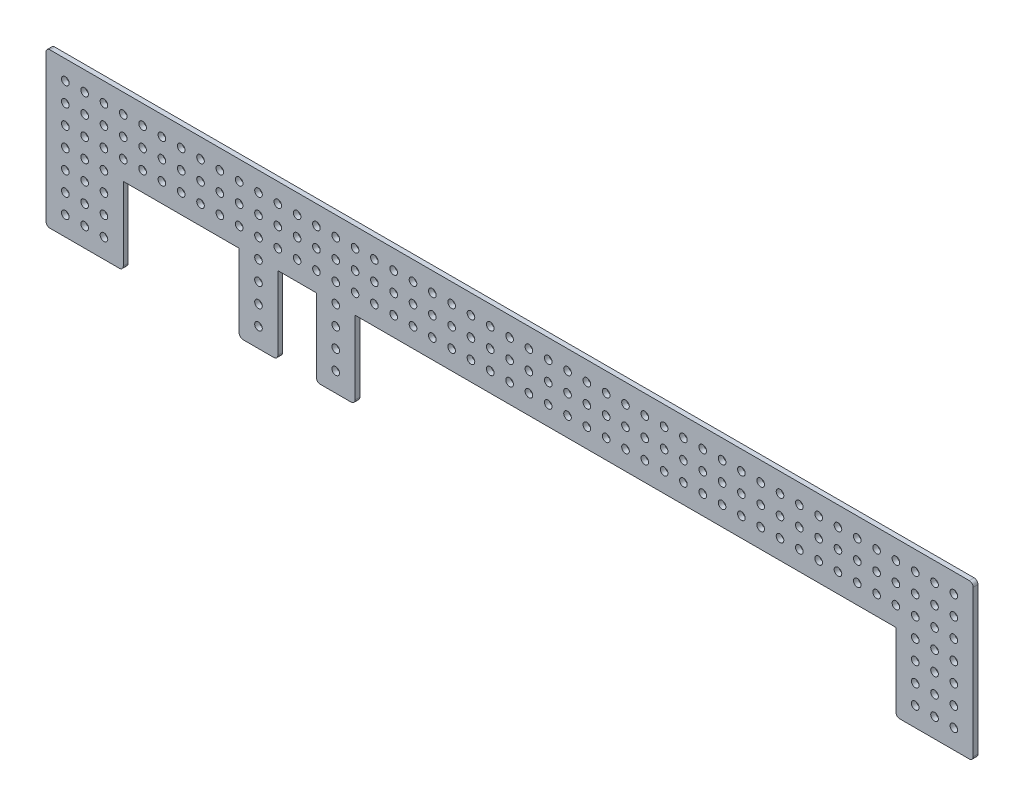
SolidWorks part; units mm, degrees
ref_plane "Front Plane" through (0, 0, 0) normal (0, 0, 1) x (1, 0, 0)
ref_plane "Top Plane" through (0, 0, 0) normal (0, 1, 0) x (1, 0, 0)
ref_plane "Right Plane" through (0, 0, 0) normal (1, 0, 0) x (0, 0, -1)
sketch "Sketch2" plane through (0, 0, 0) normal (0, 0, 1) x (1, 0, 0)
  line L1 (-478.1332, -46.4778) -> (126.3868, -46.4778)
  line L2 (-480.6732, -49.0178) -> (-480.6732, -97.2778)
  line L3 (-480.6732, -97.2778) -> (128.9268, -97.2778)
  line L4 (128.9268, -49.0178) -> (128.9268, -97.2778)
  line L5 (-480.6732, -97.2778) -> (-429.8732, -97.2778)
  line L6 (-480.6732, -97.2778) -> (-480.6732, -145.5378)
  line L7 (-478.1332, -148.0778) -> (-432.4132, -148.0778)
  line L8 (-429.8732, -97.2778) -> (-429.8732, -145.5378)
  line L9 (78.1268, -97.2778) -> (128.9268, -97.2778)
  line L10 (78.1268, -97.2778) -> (78.1268, -145.5378)
  line L11 (80.6668, -148.0778) -> (126.3868, -148.0778)
  line L12 (128.9268, -97.2778) -> (128.9268, -145.5378)
  arc A0 (78.1268, -145.5378) -> (80.6668, -148.0778) centre (80.6668, -145.5378) ccw
  arc A1 (126.3868, -148.0778) -> (128.9268, -145.5378) centre (126.3868, -145.5378) ccw
  arc A2 (126.3868, -46.4778) -> (128.9268, -49.0178) centre (126.3868, -49.0178) cw
  arc A3 (-432.4132, -148.0778) -> (-429.8732, -145.5378) centre (-432.4132, -145.5378) ccw
  arc A4 (-480.6732, -145.5378) -> (-478.1332, -148.0778) centre (-478.1332, -145.5378) ccw
  arc A5 (-478.1332, -46.4778) -> (-480.6732, -49.0178) centre (-478.1332, -49.0178) ccw
  point P16 (78.1268, -148.0778)
  point P19 (128.9268, -148.0778)
  point P22 (128.9268, -46.4778)
  point P25 (-429.8732, -148.0778)
  point P28 (-480.6732, -148.0778)
  dimension "D7" = 2.54
  dimension "D1" = 50.8
  dimension "D2" = 609.6
  dimension "D3" = 50.8
  dimension "D4" = 50.8
  dimension "3" = 50.8
  dimension "D6" = 50.8
extrude "Boss-Extrude1" add sketch "Sketch2" along normal blind 3.175 contours L4 L1 L2 L3 | L8 L3 L6 L7 | L12 L3 L10 L11 region at (-175.8732, -71.88, 0) region at (-455.2732, -122.6511, 0) region at (103.5268, -122.6511, 0)
sketch "Sketch3" plane through (0, 0, 3.175) normal (0, 0, 1) x (1, 0, 0)
  line L0 (-478.1332, -46.4778) -> (126.3868, -46.4778) construction
  line L1 (-480.6732, -49.0178) -> (-480.6732, -145.5378) construction
  line L2 (-478.1332, -148.0778) -> (-432.4132, -148.0778) construction
  line L3 (80.6668, -148.0778) -> (126.3868, -148.0778) construction
  line L4 (78.1268, -97.2778) -> (78.1268, -145.5378) construction
  circle A0 centre (-467.9732, -59.1778) radius 2.505
  circle A1 centre (-455.2732, -59.1778) radius 2.505
  circle A2 centre (-442.5732, -59.1778) radius 2.505
  circle A3 centre (-429.8732, -59.1778) radius 2.505
  circle A4 centre (-417.1732, -59.1778) radius 2.505
  circle A5 centre (-404.4732, -59.1778) radius 2.505
  circle A6 centre (-391.7732, -59.1778) radius 2.505
  circle A7 centre (-379.0732, -59.1778) radius 2.505
  circle A8 centre (-366.3732, -59.1778) radius 2.505
  circle A9 centre (-353.6732, -59.1778) radius 2.505
  circle A10 centre (-340.9732, -59.1778) radius 2.505
  circle A11 centre (-328.2732, -59.1778) radius 2.505
  circle A12 centre (-315.5732, -59.1778) radius 2.505
  circle A13 centre (-302.8732, -59.1778) radius 2.505
  circle A14 centre (-290.1732, -59.1778) radius 2.505
  circle A15 centre (-277.4732, -59.1778) radius 2.505
  circle A16 centre (-264.7732, -59.1778) radius 2.505
  circle A17 centre (-252.0732, -59.1778) radius 2.505
  circle A18 centre (-239.3732, -59.1778) radius 2.505
  circle A19 centre (-226.6732, -59.1778) radius 2.505
  circle A20 centre (-213.9732, -59.1778) radius 2.505
  circle A21 centre (-201.2732, -59.1778) radius 2.505
  circle A22 centre (-188.5732, -59.1778) radius 2.505
  circle A23 centre (-175.8732, -59.1778) radius 2.505
  circle A24 centre (-163.1732, -59.1778) radius 2.505
  circle A25 centre (-150.4732, -59.1778) radius 2.505
  circle A26 centre (-137.7732, -59.1778) radius 2.505
  circle A27 centre (-125.0732, -59.1778) radius 2.505
  circle A28 centre (-112.3732, -59.1778) radius 2.505
  circle A29 centre (-99.6732, -59.1778) radius 2.505
  circle A30 centre (-86.9732, -59.1778) radius 2.505
  circle A31 centre (-74.2732, -59.1778) radius 2.505
  circle A32 centre (-61.5732, -59.1778) radius 2.505
  circle A33 centre (-48.8732, -59.1778) radius 2.505
  circle A34 centre (-36.1732, -59.1778) radius 2.505
  circle A35 centre (-23.4732, -59.1778) radius 2.505
  circle A36 centre (-10.7732, -59.1778) radius 2.505
  circle A37 centre (1.9268, -59.1778) radius 2.505
  circle A38 centre (14.6268, -59.1778) radius 2.505
  circle A39 centre (27.3268, -59.1778) radius 2.505
  circle A40 centre (40.0268, -59.1778) radius 2.505
  circle A41 centre (52.7268, -59.1778) radius 2.505
  circle A42 centre (65.4268, -59.1778) radius 2.505
  circle A43 centre (78.1268, -59.1778) radius 2.505
  circle A44 centre (90.8268, -59.1778) radius 2.505
  circle A45 centre (103.5268, -59.1778) radius 2.505
  circle A46 centre (116.2268, -59.1778) radius 2.505
  circle A47 centre (-455.2732, -71.8778) radius 2.505
  circle A48 centre (-442.5732, -71.8778) radius 2.505
  circle A49 centre (-429.8732, -71.8778) radius 2.505
  circle A50 centre (-417.1732, -71.8778) radius 2.505
  circle A51 centre (-404.4732, -71.8778) radius 2.505
  circle A52 centre (-391.7732, -71.8778) radius 2.505
  circle A53 centre (-379.0732, -71.8778) radius 2.505
  circle A54 centre (-366.3732, -71.8778) radius 2.505
  circle A55 centre (-353.6732, -71.8778) radius 2.505
  circle A56 centre (-340.9732, -71.8778) radius 2.505
  circle A57 centre (-328.2732, -71.8778) radius 2.505
  circle A58 centre (-315.5732, -71.8778) radius 2.505
  circle A59 centre (-302.8732, -71.8778) radius 2.505
  circle A60 centre (-290.1732, -71.8778) radius 2.505
  circle A61 centre (-277.4732, -71.8778) radius 2.505
  circle A62 centre (-264.7732, -71.8778) radius 2.505
  circle A63 centre (-252.0732, -71.8778) radius 2.505
  circle A64 centre (-239.3732, -71.8778) radius 2.505
  circle A65 centre (-226.6732, -71.8778) radius 2.505
  circle A66 centre (-213.9732, -71.8778) radius 2.505
  circle A67 centre (-201.2732, -71.8778) radius 2.505
  circle A68 centre (-188.5732, -71.8778) radius 2.505
  circle A69 centre (-175.8732, -71.8778) radius 2.505
  circle A70 centre (-163.1732, -71.8778) radius 2.505
  circle A71 centre (-150.4732, -71.8778) radius 2.505
  circle A72 centre (-137.7732, -71.8778) radius 2.505
  circle A73 centre (-125.0732, -71.8778) radius 2.505
  circle A74 centre (-112.3732, -71.8778) radius 2.505
  circle A75 centre (-99.6732, -71.8778) radius 2.505
  circle A76 centre (-86.9732, -71.8778) radius 2.505
  circle A77 centre (-74.2732, -71.8778) radius 2.505
  circle A78 centre (-61.5732, -71.8778) radius 2.505
  circle A79 centre (-48.8732, -71.8778) radius 2.505
  circle A80 centre (-36.1732, -71.8778) radius 2.505
  circle A81 centre (-23.4732, -71.8778) radius 2.505
  circle A82 centre (-10.7732, -71.8778) radius 2.505
  circle A83 centre (1.9268, -71.8778) radius 2.505
  circle A84 centre (14.6268, -71.8778) radius 2.505
  circle A85 centre (27.3268, -71.8778) radius 2.505
  circle A86 centre (40.0268, -71.8778) radius 2.505
  circle A87 centre (52.7268, -71.8778) radius 2.505
  circle A88 centre (65.4268, -71.8778) radius 2.505
  circle A89 centre (78.1268, -71.8778) radius 2.505
  circle A90 centre (90.8268, -71.8778) radius 2.505
  circle A91 centre (103.5268, -71.8778) radius 2.505
  circle A92 centre (116.2268, -71.8778) radius 2.505
  circle A93 centre (-455.2732, -84.5778) radius 2.505
  circle A94 centre (-442.5732, -84.5778) radius 2.505
  circle A95 centre (-429.8732, -84.5778) radius 2.505
  circle A96 centre (-417.1732, -84.5778) radius 2.505
  circle A97 centre (-404.4732, -84.5778) radius 2.505
  circle A98 centre (-391.7732, -84.5778) radius 2.505
  circle A99 centre (-379.0732, -84.5778) radius 2.505
  circle A100 centre (-366.3732, -84.5778) radius 2.505
  circle A101 centre (-353.6732, -84.5778) radius 2.505
  circle A102 centre (-340.9732, -84.5778) radius 2.505
  circle A103 centre (-328.2732, -84.5778) radius 2.505
  circle A104 centre (-315.5732, -84.5778) radius 2.505
  circle A105 centre (-302.8732, -84.5778) radius 2.505
  circle A106 centre (-290.1732, -84.5778) radius 2.505
  circle A107 centre (-277.4732, -84.5778) radius 2.505
  circle A108 centre (-264.7732, -84.5778) radius 2.505
  circle A109 centre (-252.0732, -84.5778) radius 2.505
  circle A110 centre (-239.3732, -84.5778) radius 2.505
  circle A111 centre (-226.6732, -84.5778) radius 2.505
  circle A112 centre (-213.9732, -84.5778) radius 2.505
  circle A113 centre (-201.2732, -84.5778) radius 2.505
  circle A114 centre (-188.5732, -84.5778) radius 2.505
  circle A115 centre (-175.8732, -84.5778) radius 2.505
  circle A116 centre (-163.1732, -84.5778) radius 2.505
  circle A117 centre (-150.4732, -84.5778) radius 2.505
  circle A118 centre (-137.7732, -84.5778) radius 2.505
  circle A119 centre (-125.0732, -84.5778) radius 2.505
  circle A120 centre (-112.3732, -84.5778) radius 2.505
  circle A121 centre (-99.6732, -84.5778) radius 2.505
  circle A122 centre (-86.9732, -84.5778) radius 2.505
  circle A123 centre (-74.2732, -84.5778) radius 2.505
  circle A124 centre (-61.5732, -84.5778) radius 2.505
  circle A125 centre (-48.8732, -84.5778) radius 2.505
  circle A126 centre (-36.1732, -84.5778) radius 2.505
  circle A127 centre (-23.4732, -84.5778) radius 2.505
  circle A128 centre (-10.7732, -84.5778) radius 2.505
  circle A129 centre (1.9268, -84.5778) radius 2.505
  circle A130 centre (14.6268, -84.5778) radius 2.505
  circle A131 centre (27.3268, -84.5778) radius 2.505
  circle A132 centre (40.0268, -84.5778) radius 2.505
  circle A133 centre (52.7268, -84.5778) radius 2.505
  circle A134 centre (65.4268, -84.5778) radius 2.505
  circle A135 centre (78.1268, -84.5778) radius 2.505
  circle A136 centre (90.8268, -84.5778) radius 2.505
  circle A137 centre (103.5268, -84.5778) radius 2.505
  circle A138 centre (116.2268, -84.5778) radius 2.505
  circle A139 centre (-467.9732, -71.8778) radius 2.505
  circle A140 centre (-467.9732, -84.5778) radius 2.505
  circle A141 centre (-467.9732, -135.3778) radius 2.505
  circle A142 centre (-455.2732, -135.3778) radius 2.505
  circle A143 centre (-442.5732, -135.3778) radius 2.505
  circle A144 centre (-455.2732, -122.6778) radius 2.505
  circle A145 centre (-442.5732, -122.6778) radius 2.505
  circle A146 centre (-455.2732, -109.9778) radius 2.505
  circle A147 centre (-442.5732, -109.9778) radius 2.505
  circle A148 centre (-455.2732, -97.2778) radius 2.505
  circle A149 centre (-442.5732, -97.2778) radius 2.505
  circle A150 centre (-455.2732, -84.5778) radius 2.505
  circle A151 centre (-442.5732, -84.5778) radius 2.505
  circle A152 centre (-455.2732, -71.8778) radius 2.505
  circle A153 centre (-442.5732, -71.8778) radius 2.505
  circle A154 centre (-467.9732, -122.6778) radius 2.505
  circle A155 centre (-467.9732, -109.9778) radius 2.505
  circle A156 centre (-467.9732, -97.2778) radius 2.505
  circle A157 centre (-467.9732, -84.5778) radius 2.505
  circle A158 centre (-467.9732, -71.8778) radius 2.505
  circle A159 centre (90.8268, -135.3778) radius 2.505
  circle A160 centre (103.5268, -135.3778) radius 2.505
  circle A161 centre (116.2268, -135.3778) radius 2.505
  circle A162 centre (103.5268, -122.6778) radius 2.505
  circle A163 centre (116.2268, -122.6778) radius 2.505
  circle A164 centre (103.5268, -109.9778) radius 2.505
  circle A165 centre (116.2268, -109.9778) radius 2.505
  circle A166 centre (103.5268, -97.2778) radius 2.505
  circle A167 centre (116.2268, -97.2778) radius 2.505
  circle A168 centre (103.5268, -84.5778) radius 2.505
  circle A169 centre (116.2268, -84.5778) radius 2.505
  circle A170 centre (103.5268, -71.8778) radius 2.505
  circle A171 centre (116.2268, -71.8778) radius 2.505
  circle A172 centre (90.8268, -122.6778) radius 2.505
  circle A173 centre (90.8268, -109.9778) radius 2.505
  circle A174 centre (90.8268, -97.2778) radius 2.505
  circle A175 centre (90.8268, -84.5778) radius 2.505
  circle A176 centre (90.8268, -71.8778) radius 2.505
  dimension "5.01mm" = 5.01
  dimension "D6" = 5.01
  dimension "D11" = 5.01
  dimension "D2" = 12.7
  dimension "D3" = 12.7
  dimension "D7" = 12.7
  dimension "D8" = 12.7
  dimension "D12" = 12.7
  dimension "D13" = 12.7
  dimension "D4" = 47
  dimension "D5" = 3
  dimension "D9" = 3
  dimension "D10" = 6
  dimension "D14" = 3
  dimension "D15" = 6
extrude "Cut-Extrude1" cut sketch "Sketch3" against normal through all
sketch "Sketch4" plane through (0, 0, 3.175) normal (0, 0, 1) x (1, 0, 0)
  line L0 (-429.8732, -97.2778) -> (78.1268, -97.2778) construction
  line L1 (-353.6732, -97.2778) -> (-328.2732, -97.2778)
  line L2 (-353.6732, -97.2778) -> (-353.6732, -145.5378)
  line L3 (-351.1332, -148.0778) -> (-330.8132, -148.0778)
  line L4 (-328.2732, -97.2778) -> (-328.2732, -145.5378)
  line L5 (-302.8732, -97.2778) -> (-277.4732, -97.2778)
  line L6 (-302.8732, -97.2778) -> (-302.8732, -145.5378)
  line L7 (-300.3332, -148.0778) -> (-280.0132, -148.0778)
  line L8 (-277.4732, -97.2778) -> (-277.4732, -145.5378)
  line L9 (-429.8732, -97.2778) -> (-429.8732, -145.5378) construction
  arc A0 (-280.0132, -148.0778) -> (-277.4732, -145.5378) centre (-280.0132, -145.5378) ccw
  arc A1 (-302.8732, -145.5378) -> (-300.3332, -148.0778) centre (-300.3332, -145.5378) ccw
  arc A2 (-330.8132, -148.0778) -> (-328.2732, -145.5378) centre (-330.8132, -145.5378) ccw
  arc A3 (-353.6732, -145.5378) -> (-351.1332, -148.0778) centre (-351.1332, -145.5378) ccw
  point P14 (-277.4732, -148.0778)
  point P17 (-302.8732, -148.0778)
  point P20 (-328.2732, -148.0778)
  point P23 (-353.6732, -148.0778)
  dimension "D7" = 2.54
  dimension "D1" = 25.4
  dimension "D2" = 50.8
  dimension "D3" = 76.2
  dimension "D4" = 25.4
  dimension "D5" = 50.8
  dimension "D6" = 25.4
extrude "Boss-Extrude2" add sketch "Sketch4" against normal up to surface (3.175 mm away) up to face at (-33.6682, -71.8778, 0)
sketch "Sketch5" plane through (0, 0, 3.175) normal (0, 0, 1) x (1, 0, 0)
  line L0 (-277.4732, -145.5378) -> (-277.4732, -97.2778) construction
  line L1 (-300.3332, -148.0778) -> (-280.0132, -148.0778) construction
  line L4 (-351.1332, -148.0778) -> (-330.8132, -148.0778) construction
  line L5 (-353.6732, -97.2778) -> (-353.6732, -145.5378) construction
  circle A1 centre (-290.1732, -135.3778) radius 2.5
  circle A2 centre (-340.9732, -135.3778) radius 2.5
  circle A3 centre (-340.9732, -122.6778) radius 2.5
  circle A4 centre (-290.1732, -122.6778) radius 2.5
  circle A5 centre (-340.9732, -109.9778) radius 2.5
  circle A6 centre (-290.1732, -109.9778) radius 2.5
  circle A7 centre (-340.9732, -97.2778) radius 2.5
  circle A8 centre (-290.1732, -97.2778) radius 2.5
  dimension "D1" = 5
  dimension "D6" = 12.7
  dimension "D4" = 5
  dimension "D2" = 12.7
  dimension "D3" = 12.7
  dimension "D5" = 12.7
extrude "Cut-Extrude2" cut sketch "Sketch5" against normal through all
